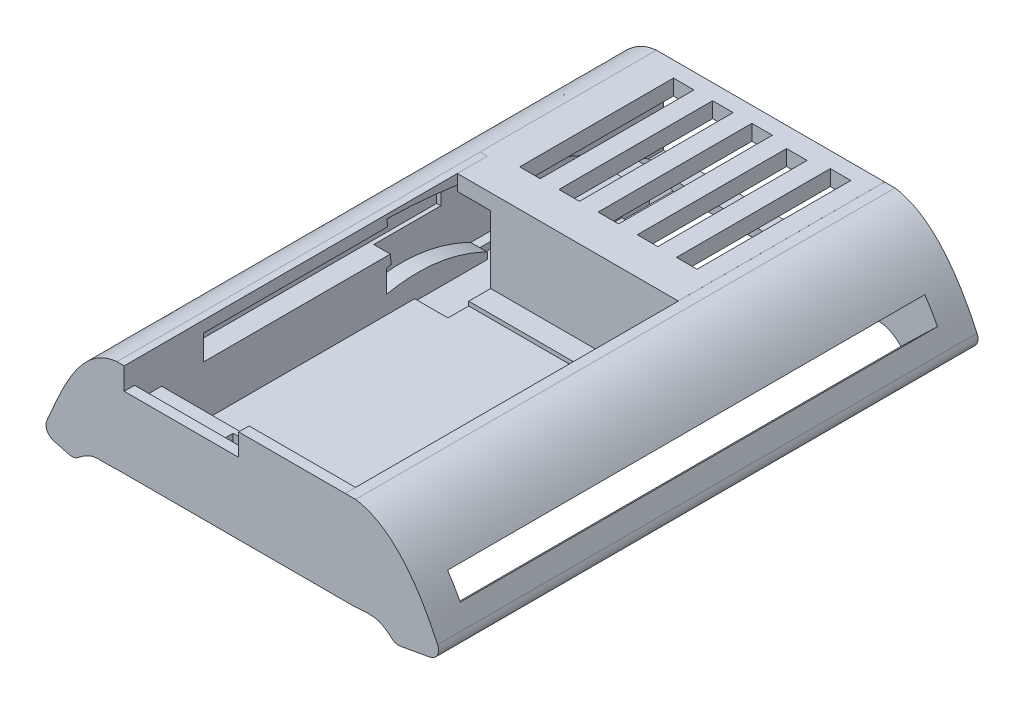
SolidWorks part; units mm, degrees
ref_plane "Front Plane" through (0, 0, 0) normal (0, 0, 1) x (1, 0, 0)
ref_plane "Top Plane" through (0, 0, 0) normal (0, 1, 0) x (1, 0, 0)
ref_plane "Right Plane" through (0, 0, 0) normal (1, 0, 0) x (0, 0, -1)
sketch "Sketch1" plane through (0, 0, 0) normal (0, 0, 1) x (1, 0, 0)
  line L0 (-4.067, -1.1908) -> (-7.2404, -0.3546)
  line L5 (0, 0) -> (22.8691, 0)
  line L9 (23.0423, 8.9983) -> (22.0423, 8.9983)
  line L10 (22.0423, 8.9983) -> (22.0423, 1)
  line L11 (22.0423, 1) -> (0.7423, 1)
  line L12 (0.7423, 1) -> (0.7423, 8.9983)
  line L13 (0.7423, 8.9983) -> (0.0423, 8.9983)
  line L14 (31.4678, -0.3546) -> (26.8755, -1.1908)
  spline S0 degree 3 poles (0.0423, 8.9983) (-4.2131, 8.6488) (-5.9624, 1.8146) (-7.2404, -0.3546) knots 0 0 0 0 1 1 1 1
  spline S1 degree 3 poles (0, 0) (-1.8708, -0.1637) (-2.2399, 0.4307) (-4.067, -1.1908) knots 0 0 0 0 1 1 1 1
  spline S2 degree 2 poles (23.0423, 8.9983) (27.8524, 8.2713) (31.4678, -0.3546) knots 0 0 0 1 1 1
  spline S3 degree 3 poles (22.8691, 0) (24.5642, 0.0744) (25.2973, 0.4291) (26.8755, -1.1908) knots 0 0 0 0 1 1 1 1
  dimension "D3" = 1
  dimension "D1" = 23
  dimension "D2" = 9
  dimension "D4" = 0.7
  dimension "D5" = 1
extrude "Boss-Extrude2" add sketch "Sketch1" along normal blind 52
fillet "Fillet2" radius 1 2 edges at (-4.067, -1.1908, 26) (-7.2404, -0.3546, 26)
ref_plane "Plane10" through (-4.3809, 3.5692, 0) normal (-0.7753, 0.6316, 0) x (0.6316, 0.7753, 0)
sketch "Sketch10" plane through (-4.3809, 3.5692, 0) normal (-0.7753, 0.6316, 0) x (0.6316, 0.7753, 0)
  line L0 (7.0029, 0) -> (-3.689, 0) construction
  line L1 (-3.0069, -50) -> (-0.6561, -50)
  line L2 (-3.0069, -50) -> (-3.0069, -4)
  line L3 (-3.0069, -4) -> (-0.6561, -4)
  line L4 (-0.6561, -50) -> (-0.6561, -4)
  point P4 (-1.8315, -4)
  dimension "D1" = 46
  dimension "D2" = 4
extrude "Cut-Extrude2" cut sketch "Sketch10" against normal blind 6 and the other way blind 3
sketch "Sketch11" plane through (0, 1, 0) normal (0, 1, 0) x (1, 0, 0)
  line L0 (22.0423, 0) -> (0.7423, 0) construction
  line L1 (3.6147, -2) -> (20.6147, -2)
  line L2 (3.6147, -2) -> (3.6147, -17)
  line L3 (3.6147, -17) -> (20.6147, -17)
  line L4 (20.6147, -2) -> (20.6147, -17)
  dimension "D1" = 17
  dimension "D2" = 15
  dimension "D3" = 2
extrude "Peltier" cut sketch "Sketch11" against normal blind 10
sketch "Sketch12" plane through (0, 1, 0) normal (0, 1, 0) x (1, 0, 0)
  line L0 (0.7423, -52) -> (0.7423, 0) construction
  line L1 (0.7423, -22) -> (21.7423, -22)
  line L2 (0.7423, -22) -> (0.7423, -51)
  line L3 (0.7423, -51) -> (21.7423, -51)
  line L4 (21.7423, -22) -> (21.7423, -51)
  line L5 (22.0423, -52) -> (0.7423, -52) construction
  dimension "D1" = 29
  dimension "D2" = 21
  dimension "D3" = 1
extrude "Battery" cut sketch "Sketch12" against normal blind 0.4
sketch "Sketch14" plane through (0, 1, 0) normal (0, 1, 0) x (1, 0, 0)
  line L1 (22.0423, -52) -> (0.7423, -52)
  line L2 (22.0423, -52) -> (22.0423, -51)
  line L3 (22.0423, -51) -> (0.7423, -51)
  line L4 (0.7423, -52) -> (0.7423, -51)
extrude "Boss-Extrude4" add sketch "Sketch14" along normal blind 7.9999
sketch "Sketch15" plane through (3.6147, 0, 0) normal (1, 0, 0) x (0, 0, -1)
  line L0 (-2, 1) -> (-17, 1) construction
  line L1 (-17, 0.3705) -> (-13.7023, 0.3705)
  line L2 (-17, 0.3705) -> (-17, 1)
  line L3 (-17, 1) -> (-13.7023, 1)
  line L4 (-13.7023, 0.3705) -> (-13.7023, 1)
extrude "Cut-Extrude5" cut sketch "Sketch15" against normal blind 3.6
sketch "Sketch16" plane through (3.6147, 0, 0) normal (1, 0, 0) x (0, 0, -1)
  line L0 (-2, 1) -> (-13.7023, 1) construction
  line L1 (-1.4649, 0.3306) -> (-4.2604, 0.3306)
  line L2 (-1.4649, 0.3306) -> (-1.4649, 1)
  line L3 (-1.4649, 1) -> (-4.2604, 1)
  line L4 (-4.2604, 0.3306) -> (-4.2604, 1)
extrude "Cut-Extrude6" cut sketch "Sketch16" against normal blind 4.337
fillet "Fillet3" radius 1 2 edges at (3.6147, 0.3306, 3.1302) (3.6147, 0.3705, 15.3511)
sketch "Sketch17" plane through (0.7423, 0, 0) normal (1, 0, 0) x (0, 0, -1)
  line L0 (-26.6799, 8.6073) -> (-26.2563, 4.6003)
  line L1 (-11.9564, 1) -> (-1.4649, 1)
  line L2 (-13.7023, 1) -> (-4.2604, 1) construction
  spline S0 degree 2 poles (-1.4649, 1) (-12.8352, 8.3747) (-26.6799, 8.6073) knots 0 0 0 1 1 1
  spline S1 degree 2 poles (-11.9564, 1) (-18.174, 5.6459) (-26.2563, 4.6003) knots 0 0 0 1 1 1
  point P5 (-4.2604, 1)
  point P8 (-12.38, 1)
  point P12 (-16.235, 3.4351)
extrude "Cut-Extrude7" cut sketch "Sketch17" against normal blind 1.6
sketch "Sketch18" plane through (0.7423, 0, 0) normal (1, 0, 0) x (0, 0, -1)
  line L0 (-26.7094, 2.3332) -> (-26.7094, 4.4721)
  line L1 (-17, 1) -> (-10.0823, 1)
  spline S0 degree 2 poles (-10.0823, 1) (-18.1477, 7.1317) (-26.7094, 4.4721) knots 0 0 0 1 1 1
  spline S1 degree 2 poles (-17, 1) (-21.7034, 3.3547) (-26.7094, 2.3332) knots 0 0 0 1 1 1
  point P5 (-10.0823, 1)
extrude "Cut-Extrude8" cut sketch "Sketch18" against normal blind 1.6
fillet "Fillet4" radius 1 1 edges at (26.8755, -1.1908, 26)
fillet "Fillet5" radius 1 1 edges at (31.4678, -0.3546, 26)
sketch "Sketch19" plane through (0, 0, 51) normal (0, 0, -1) x (-1, 0, 0)
  line L0 (-0.7423, 0.6) -> (-0.7423, 8.9983) construction
  line L1 (-0.7423, 4.5) -> (-22.0423, 4.5)
  line L2 (-0.7423, 4.5) -> (-0.7423, 5.5)
  line L3 (-0.7423, 5.5) -> (-22.0423, 5.5)
  line L4 (-22.0423, 4.5) -> (-22.0423, 5.5)
  line L5 (-22.0423, 8.9983) -> (-22.0423, 1) construction
  line L6 (-0.7423, 0.6) -> (-21.7423, 0.6) construction
  dimension "D1" = 1
  dimension "D2" = 3.9
extrude "Boss-Extrude5" add sketch "Sketch19" along normal blind 2.6
sketch "Sketch20" plane through (0, 5.5, 0) normal (0, 1, 0) x (1, 0, 0)
  line L0 (0.7423, -51) -> (22.0423, -51) construction
  line L1 (15.7498, -51) -> (8.1239, -51)
  line L2 (15.7498, -51) -> (15.7498, -48.879)
  line L3 (15.7498, -48.879) -> (8.1239, -48.879)
  line L4 (8.1239, -51) -> (8.1239, -48.879)
extrude "Cut-Extrude9" cut sketch "Sketch20" against normal blind 2.6
sketch "Sketch21" plane through (0, 1, 0) normal (0, 1, 0) x (1, 0, 0)
  line L0 (22.0423, -51) -> (22.0423, 0) construction
  line L1 (22.0423, -17) -> (0.7423, -17)
  line L2 (22.0423, -17) -> (22.0423, -19.8861)
  line L3 (22.0423, -19.8861) -> (0.7423, -19.8861)
  line L4 (0.7423, -17) -> (0.7423, -19.8861)
  line L5 (0.7423, -22) -> (0.7423, -17) construction
extrude "Boss-Extrude6" add sketch "Sketch21" along normal blind 8
sketch "Sketch22" plane through (22.0423, 0, 0) normal (-1, 0, 0) x (0, 0, 1)
  line L0 (0, 8.9983) -> (0, 1) construction
  line L1 (17, 9) -> (0, 9)
  line L2 (17, 9) -> (17, 7.5)
  line L3 (17, 7.5) -> (0, 7.5)
  line L4 (0, 9) -> (0, 7.5)
  dimension "D1" = 1.5
extrude "Boss-Extrude7" add sketch "Sketch22" along normal blind 22
sketch "Sketch23" plane through (0.7423, 0, 0) normal (1, 0, 0) x (0, 0, -1)
  line L0 (-48.4, 5.5) -> (-51, 5.5) construction
  line L1 (-44.3676, 5.5) -> (-19.8861, 5.5)
  line L2 (-44.3676, 5.5) -> (-44.3676, 7.9035)
  line L3 (-44.3676, 7.9035) -> (-19.8861, 7.9035)
  line L4 (-19.8861, 5.5) -> (-19.8861, 7.9035)
  line L5 (-19.8861, 8.9983) -> (-19.8861, 8.0406) construction
extrude "Cut-Extrude10" cut sketch "Sketch23" against normal blind 2
sketch "Sketch24" plane through (20.6147, 0, 0) normal (-1, 0, 0) x (0, 0, 1)
  line L0 (17, 0) -> (17, 1) construction
  line L1 (2, 0) -> (17, 0)
  line L2 (2, 0) -> (2, 0.2114)
  line L3 (2, 0.2114) -> (17, 0.2114)
  line L4 (17, 0) -> (17, 0.2114)
extrude "Boss-Extrude8" add sketch "Sketch24" along normal blind 2
sketch "Sketch25" plane through (3.6147, 0, 0) normal (1, 0, 0) x (0, 0, -1)
  line L0 (-4.2604, 0) -> (-13.7023, 0) construction
  line L1 (-6.8876, 0) -> (-11.6748, 0)
  line L2 (-6.8876, 0) -> (-6.8876, 0.2374)
  line L3 (-6.8876, 0.2374) -> (-11.6748, 0.2374)
  line L4 (-11.6748, 0) -> (-11.6748, 0.2374)
extrude "Boss-Extrude9" add sketch "Sketch25" along normal blind 2
sketch "Sketch26" plane through (0, 0, 51) normal (0, 0, -1) x (-1, 0, 0)
  line L0 (-0.7423, 5.5) -> (-0.7423, 8.9983) construction
  line L1 (-0.7423, 6.8737) -> (-11.7785, 6.8737)
  line L2 (-0.7423, 6.8737) -> (-0.7423, 8.9999)
  line L3 (-0.7423, 8.9999) -> (-11.7785, 8.9999)
  line L4 (-11.7785, 6.8737) -> (-11.7785, 8.9999)
  line L5 (-22.0423, 8.9999) -> (-0.7423, 8.9999) construction
extrude "Cut-Extrude11" cut sketch "Sketch26" against normal blind 2
ref_plane "Plane7" through (1.1804, 5.0597, 0) normal (0.2272, 0.9739, 0) x (0.9739, -0.2272, 0)
ref_plane "Plane8" through (16.4013, 15.8642, 0) normal (0.7188, 0.6952, 0) x (0, 0, -1)
sketch "Sketch27" plane through (16.4013, 15.8642, 0) normal (0.7188, 0.6952, 0) x (0, 0, -1)
  line L0 (0, -19.0571) -> (0, -15.8995) construction
  line L1 (-3, -16.8482) -> (-49, -16.8482)
  line L2 (-3, -16.8482) -> (-3, -19.1782)
  line L3 (-3, -19.1782) -> (-49, -19.1782)
  line L4 (-49, -16.8482) -> (-49, -19.1782)
  dimension "D1" = 46
  dimension "D2" = 3
  dimension "D3" = 2.33
extrude "Cut-Extrude12" cut sketch "Sketch27" against normal blind 11 and the other way blind 2
sketch "Sketch28" plane through (0, 9, 0) normal (0, 1, 0) x (1, 0, 0)
  line L1 (20.2889, -1.507) -> (18.3099, -1.507)
  line L2 (20.2889, -1.507) -> (20.2889, -16.3291)
  line L3 (20.2889, -16.3291) -> (18.3099, -16.3291)
  line L4 (18.3099, -1.507) -> (18.3099, -16.3291)
  line L5 (16.5099, -16.3291) -> (14.5309, -16.3291)
  line L6 (16.5099, -16.3291) -> (16.5099, -1.9398)
  line L7 (16.5099, -1.9398) -> (14.5309, -1.9398)
  line L8 (14.5309, -16.3291) -> (14.5309, -1.9398)
  line L9 (12.7309, -1.507) -> (10.752, -1.507)
  line L10 (12.7309, -1.507) -> (12.7309, -16.3291)
  line L11 (12.7309, -16.3291) -> (10.752, -16.3291)
  line L12 (10.752, -1.507) -> (10.752, -16.3291)
  line L13 (8.952, -16.3291) -> (6.973, -16.3291)
  line L14 (8.952, -16.3291) -> (8.952, -1.507)
  line L15 (8.952, -1.507) -> (6.973, -1.507)
  line L16 (6.973, -16.3291) -> (6.973, -1.507)
  line L17 (5.173, -1.507) -> (3.194, -1.507)
  line L18 (5.173, -1.507) -> (5.173, -16.3291)
  line L19 (5.173, -16.3291) -> (3.194, -16.3291)
  line L20 (3.194, -1.507) -> (3.194, -16.3291)
  dimension "D1" = 1.8
  dimension "D2" = 1.8
  dimension "D3" = 1.8
  dimension "D4" = 1.8
extrude "Cut-Extrude13" cut sketch "Sketch28" against normal blind 3
sketch "Sketch29" plane through (0, 0, 17) normal (0, 0, -1) x (-1, 0, 0)
  line L0 (-0.7423, 7.5) -> (-22.0423, 7.5) construction
  line L1 (-3.9524, 7.5) -> (-0.7423, 7.5)
  line L2 (-3.9524, 7.5) -> (-3.9524, 0.3705)
  line L3 (-3.9524, 0.3705) -> (-0.7423, 0.3705)
  line L4 (-0.7423, 7.5) -> (-0.7423, 0.3705)
  line L5 (-0.0147, 0.3705) -> (-2.8377, 0.3705) construction
extrude "Cut-Extrude14" cut sketch "Sketch29" against normal blind 7
